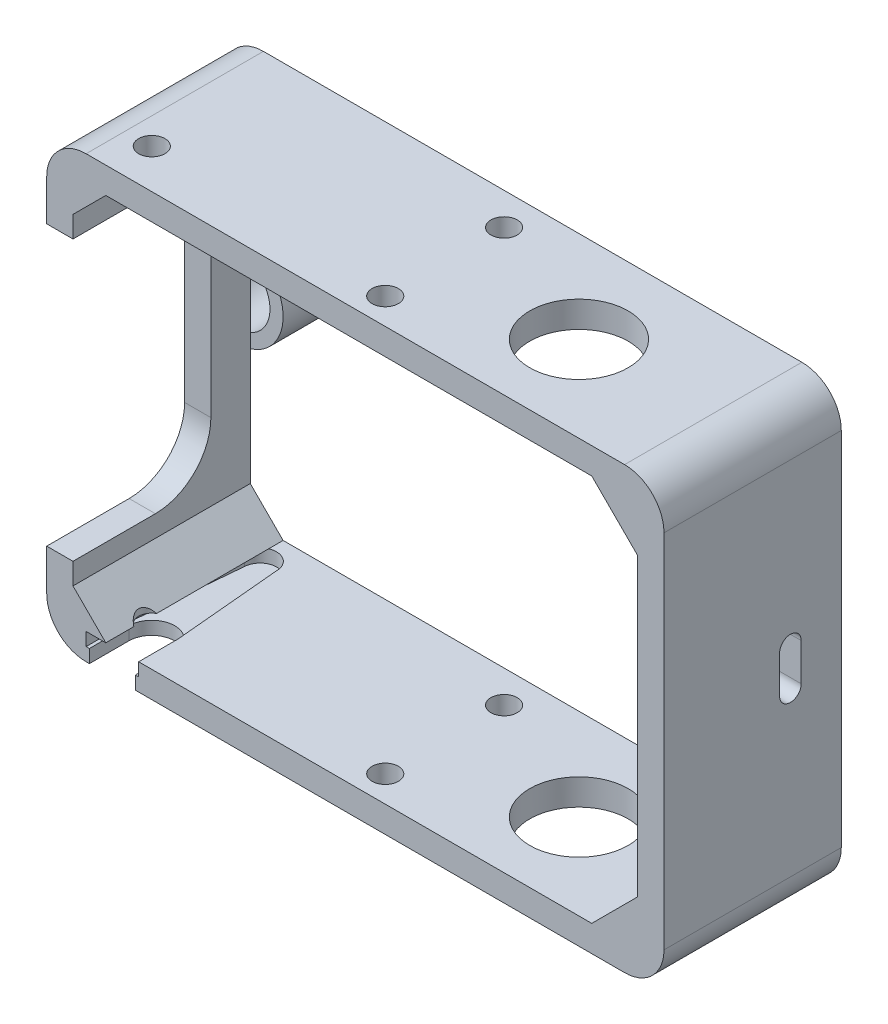
SolidWorks part; units mm, degrees
ref_plane "Alzado" through (0, 0, 0) normal (0, 0, 1) x (1, 0, 0)
ref_plane "Planta" through (0, 0, 0) normal (0, 1, 0) x (1, 0, 0)
ref_plane "Vista lateral" through (0, 0, 0) normal (1, 0, 0) x (0, 0, -1)
sketch "Croquis1" plane through (0, 0, 0) normal (0, 0, 1) x (1, 0, 0)
  line L0 (35.1, -11.25) -> (-54.9, -11.25) construction
  line L1 (35.1, -11.25) -> (35.1, 51.75) construction
  line L2 (-54.9, -11.25) -> (-54.9, 51.75) construction
  line L3 (35.1, 51.75) -> (-54.9, 51.75) construction
  line L4 (37.1, -13.25) -> (-56.9, -13.25)
  line L5 (-56.9, -13.25) -> (-56.9, 53.75)
  line L6 (37.1, 53.75) -> (-56.9, 53.75)
  line L7 (37.1, -13.25) -> (37.1, 53.75)
  line L8 (33.1, -9.25) -> (-52.9, -9.25)
  line L9 (-52.9, -9.25) -> (-52.9, 49.75)
  line L10 (33.1, 49.75) -> (-52.9, 49.75)
  line L11 (33.1, -9.25) -> (33.1, 49.75)
  dimension "D3" = 90
  dimension "D4" = 63
  dimension "D1" = 2
  dimension "D2" = 2
extrude "Saliente-Extruir1" add sketch "Croquis1" against normal blind 24 and the other way blind 3
chamfer "Chaflán1" distance 5 angle 45 2 edges at (-52.9, -9.25, -10.5) (-52.9, 49.75, -10.5)
fillet "Redondeo2" [suppressed] radius 7
sketch "Croquis10" plane through (0, 53.75, 0) normal (0, 1, 0) x (1, 0, 0)
  line L0 (-56.9, -3) -> (-56.9, 24) construction
  line L4 (37.1, -3) -> (-56.9, -3) construction
  circle A0 centre (-46.9, 3) radius 2
  point P5 (0, 0)
  dimension "D1" = 4
  dimension "D2" = 10
  dimension "D3" = 6
extrude "Cortar-Extruir6" cut sketch "Croquis10" against normal through all
sketch "Croquis2" plane through (0, -13.25, 0) normal (0, -1, 0) x (-1, 0, 0)
  line L0 (56.9, -3) -> (-37.1, -3) construction
  line L6 (43.4, 2.9999) -> (43.4001, -3)
  line L7 (43.4001, -3) -> (50.4, -3)
  line L8 (50.4, -3) -> (50.4, 3)
  arc A0 (50.4, 3) -> (43.4, 2.9999) centre (46.9, 3) ccw
  point P0 (43.4, -3)
extrude "Cortar-Extruir1" cut sketch "Croquis2" against normal up to surface (4 mm away) up to face at (-20.4, -9.25, -8)
sketch "Croquis9" plane through (0, -9.25, 0) normal (0, 1, 0) x (1, 0, 0)
  line L0 (-49.3957, 19.6465) -> (-50.9, 3)
  line L1 (-44.4, 19.5) -> (-42.9, 3)
  line L2 (-46.9, 3) -> (-46.9, 19.5) construction
  line L6 (-50.9, 3) -> (-50.9, -3)
  line L7 (37.1, -3) -> (-56.9, -3) construction
  line L8 (-50.9, -3) -> (-42.9, -3)
  line L9 (-42.9, -3) -> (-42.9, 3)
  arc A1 (-44.4, 19.5) -> (-49.3957, 19.6465) centre (-46.9, 19.5) ccw
  circle A2 centre (-46.9, 3) radius 4 construction
  dimension "D1" = 2.5
  dimension "D2" = 8
  dimension "D3" = 16.5
extrude "Cortar-Extruir5" cut sketch "Croquis9" against normal blind 2
sketch "Croquis4" plane through (-52.9, 0, 0) normal (1, 0, 0) x (0, 0, -1)
  line L0 (-3, 20.25) -> (24, 20.25) construction
  line L1 (-3, -13.25) -> (-3, 53.75) construction
  line L2 (24, -13.25) -> (24, 53.75) construction
sketch "Croquis5" plane through (-56.9, 0, 0) normal (-1, 0, 0) x (0, 0, 1)
  line L0 (-9.55, 33.05) -> (-9.55, 7.45) construction
  line L2 (-18, 33.05) -> (-18, 7.45)
  line L3 (-9.55, 41.5) -> (3, 41.5)
  line L4 (3, 53.75) -> (3, -13.25) construction
  line L5 (3, 41.5) -> (3, -1)
  line L6 (3, -1) -> (-9.55, -1)
  line L7 (-24, 53.75) -> (-24, -13.25) construction
  arc A0 (-9.55, 41.5) -> (-18, 33.05) centre (-9.55, 33.05) ccw
  arc A1 (-18, 7.45) -> (-9.55, -1) centre (-9.55, 7.45) ccw
  point P4 (-9.3, 20.05)
  dimension "D1" = 25.6
  dimension "D2" = 42.5
  dimension "D3" = 6
extrude "Cortar-Extruir2" cut sketch "Croquis5" against normal up to next
sketch "Croquis6" plane through (-56.9, 0, 0) normal (-1, 0, 0) x (0, 0, 1)
  line L0 (-16.25, 23.1) -> (-16.25, 17.4) construction
  line L1 (-14.6069, 23.1) -> (-14.6069, 17.4)
  line L2 (-17.8931, 23.1) -> (-17.8931, 17.4)
  arc A0 (-14.6069, 23.1) -> (-17.8931, 23.1) centre (-16.25, 23.1) ccw
  arc A1 (-17.8931, 17.4) -> (-14.6069, 17.4) centre (-16.25, 17.4) ccw
  point P4 (-16.25, 20.25)
extrude "Cortar-Extruir3" cut sketch "Croquis6" against normal up to next
fillet "Redondeo1" radius 6 2 edges at (-56.9, -13.25, -10.5) (-56.9, 53.75, -10.5)
fillet "Redondeo3" radius 6 2 edges at (37.1, -13.25, -10.5) (37.1, 53.75, -10.5)
sketch "Croquis12" plane through (0, -13.25, 0) normal (0, -1, 0) x (1, 0, 0)
  line L0 (-9.35, -1) -> (-9.35, -19.1) construction
  line L1 (-9.35, -19.1) -> (11.1, -10.05) construction
  line L2 (11.1, -10.05) -> (-9.35, -1) construction
  line L3 (31.1, -24) -> (31.1, 3) construction
  line L4 (-43.4001, 3) -> (31.1, 3) construction
  circle A0 centre (11.1, -10.05) radius 7.5
  circle A1 centre (-9.35, -1) radius 2
  circle A2 centre (-9.35, -19.1) radius 2
  dimension "D1" = 15
  dimension "D2" = 4
  dimension "D3" = 4
  dimension "D4" = 18.1
  dimension "D5" = 20.45
  dimension "D6" = 66.129
  dimension "D7" = 4
  dimension "D9" = 20
extrude "Cortar-Extruir7" cut sketch "Croquis12" against normal blind 70
chamfer "Chaflán2" distance 7 angle 45 2 edges at (33.1, 49.75, -10.5) (33.1, -9.25, -10.5)
sketch "Croquis13" plane through (0, 0, 3) normal (0, 0, 1) x (1, 0, 0)
  line L0 (-52.9, 49.75) -> (33.1, 49.75) construction
  line L1 (-52.9, 49.75) -> (-52.9, -9.25) construction
  line L2 (33.1, 49.75) -> (33.1, -9.25) construction
  line L3 (-52.9, -9.25) -> (33.1, -9.25) construction
  line L4 (-56.9, 47.75) -> (-56.9, 41.5) construction
  line L5 (31.1, 53.75) -> (-50.9, 53.75) construction
  line L6 (-43.4001, -13.25) -> (31.1, -13.25) construction
  line L7 (37.1, -7.25) -> (37.1, 47.75) construction
  dimension "D1" = 4
  dimension "D2" = 4
  dimension "D3" = 4
  dimension "D4" = 4
sketch "Croquis14" plane through (0, 0, -24) normal (0, 0, -1) x (-1, 0, 0)
  line L0 (56.9, 20.25) -> (52.9, 20.25) construction
  line L1 (56.9, 47.75) -> (56.9, -7.25) construction
  line L2 (52.9, 49.75) -> (52.9, -9.25) construction
  circle A0 centre (54.9, 20.25) radius 7
  circle A1 centre (54.9, 20.25) radius 5
  dimension "D1" = 2
extrude "Saliente-Extruir2" add sketch "Croquis14" along normal blind 10
